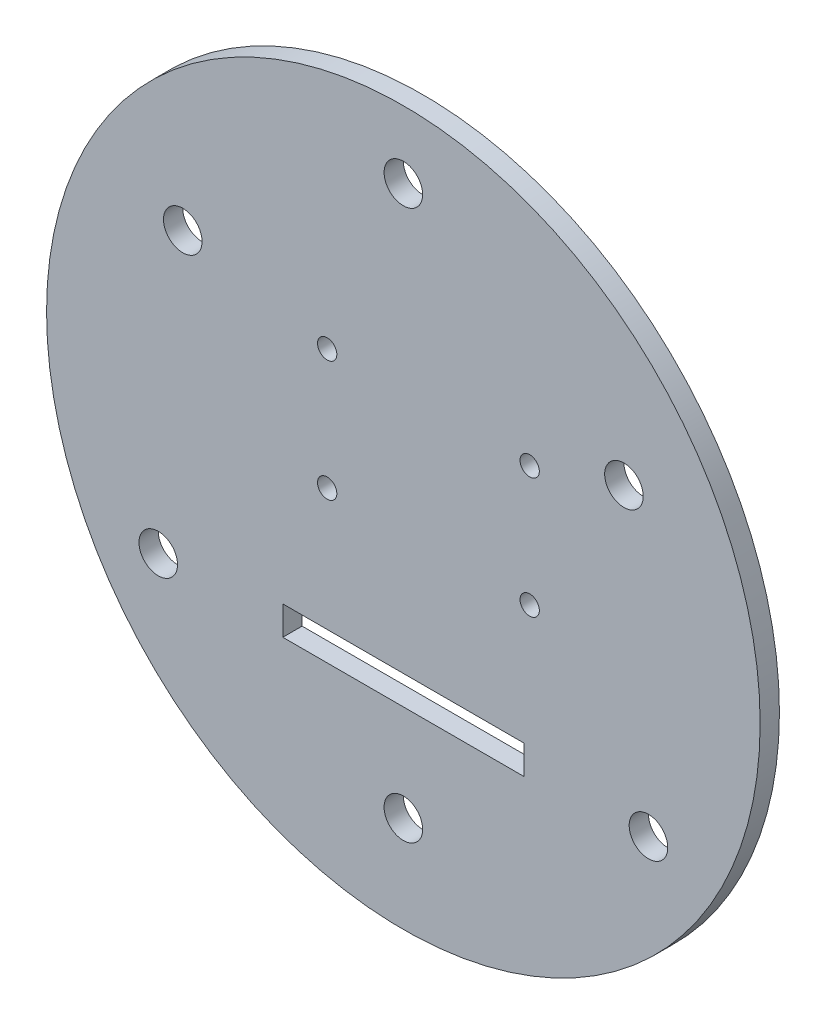
SolidWorks part; units mm, degrees
ref_plane "Plan de face" through (0, 0, 0) normal (0, 0, 1) x (1, 0, 0)
ref_plane "Plan de dessus" through (0, 0, 0) normal (0, 1, 0) x (1, 0, 0)
ref_plane "Plan de droite" through (0, 0, 0) normal (1, 0, 0) x (0, 0, -1)
sketch "Esquisse1" plane through (0, 0, 0) normal (0, 0, 1) x (1, 0, 0)
  line L0 (0, 0) -> (0, -27) construction
  line L1 (0, -27) -> (0, 30) construction
  line L2 (0, 0) -> (25.4165, -15.9375) construction
  line L3 (25.4165, -15.9375) -> (-22.8748, 14.3437) construction
  line L4 (-25.4165, -15.9375) -> (0, 0) construction
  line L5 (0, 0) -> (22.8748, 14.3437) construction
  line L6 (0, 30) -> (25.4165, -15.9375) construction
  line L8 (12.5, -14) -> (-12.5, -14)
  line L9 (12.5, -14) -> (12.5, -17)
  line L10 (12.5, -17) -> (-12.5, -17)
  line L11 (-12.5, -14) -> (-12.5, -17)
  circle A0 centre (0, 0) radius 37
  circle A1 centre (0, 30) radius 2
  circle A2 centre (-22.8748, 14.3437) radius 2
  circle A3 centre (-25.4165, -15.9375) radius 2
  circle A4 centre (0, -27) radius 2
  circle A5 centre (25.4165, -15.9375) radius 2
  circle A6 centre (22.8748, 14.3437) radius 2
  dimension "D1" = 74
  dimension "D11" = 4
  dimension "D12" = 4
  dimension "D13" = 4
  dimension "D14" = 4
  dimension "D15" = 4
  dimension "D16" = 4
  dimension "D2" = 27
  dimension "D3" = 57
  dimension "D4" = 57
  dimension "D5" = 30
  dimension "D6" = 30
  dimension "D7" = 27
  dimension "D8" = 52.5
  dimension "D9" = 52.5
  dimension "D10" = 47.25
  dimension "D17" = 25
  dimension "D18" = 3
  dimension "D19" = 10
  dimension "D20" = 12.5
extrude "Boss.-Extru.1" add sketch "Esquisse1" along normal blind 2
sketch "Esquisse2" plane through (0, 0, 0) normal (0, 0, -1) x (-1, 0, 0)
  line L0 (-16.55, 14.9) -> (-16.55, -13.5)
  line L1 (-12.55, 14.9) -> (12.55, 14.9)
  line L2 (-12.55, 14.9) -> (-12.55, -9.5)
  line L3 (-12.55, -9.5) -> (12.55, -9.5)
  line L4 (12.55, 14.9) -> (12.55, -9.5)
  line L5 (-16.55, -13.5) -> (16.55, -13.5)
  line L6 (16.55, -13.5) -> (16.55, 14.9)
  line L7 (16.55, 14.9) -> (12.55, 14.9)
  line L8 (-16.55, 14.9) -> (-12.55, 14.9)
  point P0 (0, 0)
  dimension "D1" = 25.1
  dimension "D2" = 9.5
  dimension "D3" = 24.4
  dimension "D4" = 4
  dimension "D5" = 4
  dimension "D6" = 4
  dimension "D7" = 12.55
extrude "Boss.-Extru.2" add sketch "Esquisse2" along normal blind 15 contours L8 L0 L5 L6 L7 L4 L3 L2 region at (14.55, 14.4639, 0)
sketch "Esquisse3" plane through (-12.55, 0, 0) normal (1, 0, 0) x (0, 0, -1)
  line L0 (15, 14.9) -> (0, 14.9) construction
  line L1 (10.625, 14.9) -> (8.625, 14.9)
  line L2 (10.625, 14.9) -> (10.625, -13.5)
  line L3 (10.625, -13.5) -> (8.625, -13.5)
  line L4 (8.625, 14.9) -> (8.625, -13.5)
  line L5 (15, -13.5) -> (0, -13.5) construction
  line L6 (0, 14.9) -> (7.5, 14.9) construction
  line L8 (5.625, 14.9) -> (7.625, 14.9)
  line L9 (5.625, 14.9) -> (5.625, -13.5)
  line L10 (5.625, -13.5) -> (7.625, -13.5)
  line L11 (7.625, 14.9) -> (7.625, -13.5)
  line L12 (8, 14.9) -> (8, -13.5) construction
  dimension "D1" = 2
  dimension "D2" = 0.625
  dimension "D3" = 2
  dimension "D4" = 1
  dimension "D5" = 0.375
  dimension "D6" = 0.5
extrude "Boss.-Extru.3" add sketch "Esquisse3" along normal blind 2.25 contours L11 L10 L9 L8 | L2 L3 L4 L1
sketch "Esquisse5" plane through (12.55, 0, 0) normal (-1, 0, 0) x (0, 0, 1)
  line L1 (-10.625, 14.9) -> (-8.625, 14.9)
  line L2 (-10.625, 14.9) -> (-10.625, -9.5)
  line L3 (-10.625, -9.5) -> (-8.625, -9.5)
  line L4 (-8.625, 14.9) -> (-8.625, -9.5)
  line L5 (-7.625, 14.9) -> (-5.625, 14.9)
  line L6 (-7.625, 14.9) -> (-7.625, -9.5)
  line L7 (-7.625, -9.5) -> (-5.625, -9.5)
  line L8 (-5.625, 14.9) -> (-5.625, -9.5)
extrude "Boss.-Extru.4" add sketch "Esquisse5" along normal blind 2.25
sketch "Esquisse7" plane through (0, 0, -15) normal (0, 0, -1) x (-1, 0, 0)
  line L1 (-16.55, 14.9) -> (16.55, 14.9)
  line L2 (-16.55, 14.9) -> (-16.55, -13.5)
  line L3 (-16.55, -13.5) -> (16.55, -13.5)
  line L4 (16.55, 14.9) -> (16.55, -13.5)
extrude "Boss.-Extru.5" add sketch "Esquisse7" against normal blind 1
sketch "Esquisse8" plane through (0, 0, -15) normal (0, 0, -1) x (-1, 0, 0)
  line L1 (-7.5, 7.5) -> (7.5, 7.5)
  line L2 (-7.5, 7.5) -> (-7.5, -7.5)
  line L3 (-7.5, -7.5) -> (7.5, -7.5)
  line L4 (7.5, 7.5) -> (7.5, -7.5)
  line L5 (-7.5, 7.5) -> (7.5, -7.5) construction
  line L6 (-7.5, -7.5) -> (7.5, 7.5) construction
  point P0 (0, 0)
  dimension "D1" = 15
  dimension "D2" = 15
extrude "Enlèv. mat.-Extru.1" cut sketch "Esquisse8" against normal blind 3 contours L3 L4 L1 L2
sketch "Esquisse9" plane through (0, -13.5, 0) normal (0, -1, 0) x (1, 0, 0)
  line L0 (16.55, 0) -> (-16.55, 0) construction
  line L1 (-10.5, -4.4) -> (10.5, -4.4)
  line L2 (-10.5, -4.4) -> (-10.5, -6.9)
  line L3 (-10.5, -6.9) -> (10.5, -6.9)
  line L4 (10.5, -4.4) -> (10.5, -6.9)
  line L6 (10.5, -4.4) -> (10.5, 0) construction
  line L7 (10.5, 0) -> (-10.5, 0) construction
  line L8 (-10.5, 0) -> (-10.5, -4.4) construction
  point P6 (0, -4.4)
  dimension "D1" = 21
  dimension "D2" = 2.5
  dimension "D3" = 4.4
  dimension "D4" = 0
extrude "Enlèv. mat.-Extru.2" cut sketch "Esquisse9" against normal blind 3 contours L1 L4 L3 L2
sketch "Esquisse10" plane through (0, 0, 2) normal (0, 0, 1) x (1, 0, 0)
  line L0 (16.55, -13.5) -> (-16.55, -13.5) construction
  line L1 (-16.55, -13.5) -> (-16.55, 14.9) construction
  line L2 (16.55, 14.9) -> (16.55, -13.5) construction
  line L3 (16.55, 14.9) -> (12.55, 14.9) construction
  line L4 (-16.55, 14.9) -> (-12.55, 14.9) construction
  circle A0 centre (-14.55, 8.9) radius 1
  circle A1 centre (-14.55, -11.5) radius 1
  circle A2 centre (14.55, -11.5) radius 1
  circle A3 centre (14.55, 8.9) radius 1
  dimension "D1" = 2
  dimension "D2" = 2
  dimension "D3" = 2
  dimension "D4" = 2
  dimension "D5" = 2
  dimension "D6" = 2
  dimension "D7" = 2
  dimension "D8" = 2
  dimension "D9" = 2
  dimension "D10" = 6
  dimension "D11" = 6
  dimension "D12" = 2
sketch "Esquisse11" plane through (0, 0, -15) normal (0, 0, -1) x (-1, 0, 0)
  line L1 (16.55, 14.9) -> (-16.55, 14.9)
  line L2 (16.55, 14.9) -> (16.55, -13.5)
  line L3 (16.55, -13.5) -> (-16.55, -13.5)
  line L4 (-16.55, 14.9) -> (-16.55, -13.5)
extrude "Enlèv. mat.-Extru.4" cut sketch "Esquisse11" against normal blind 15
sketch "Sketch1" plane through (0, 0, 0) normal (0, 0, -1) x (-1, 0, 0)
  line L1 (-6.6, -5.3) -> (1.4, -5.3) construction
  line L2 (-6.6, -5.3) -> (-6.6, 2.7) construction
  line L3 (-6.6, 2.7) -> (1.4, 2.7) construction
  line L4 (1.4, -5.3) -> (1.4, 2.7) construction
  line L5 (-6.6, -5.3) -> (1.4, 2.7) construction
  line L6 (-6.6, 2.7) -> (1.4, -5.3) construction
  line L7 (-13.1, -1.3) -> (7.9, -1.3) construction
  line L8 (-13.1, -1.3) -> (-13.1, 11.2) construction
  line L9 (-13.1, 11.2) -> (7.9, 11.2) construction
  line L10 (7.9, -1.3) -> (7.9, 11.2) construction
  line L11 (-13.1, -1.3) -> (7.9, 11.2) construction
  line L12 (-13.1, 11.2) -> (7.9, -1.3) construction
  circle A0 centre (0, 0) radius 37
  circle A1 centre (0, 0) radius 39.3 construction
  circle A2 centre (0, 0) radius 37 construction
  circle A3 centre (7.9, -1.3) radius 1
  circle A4 centre (-13.1, -1.3) radius 1
  circle A5 centre (-13.1, 11.2) radius 1.75
  circle A6 centre (7.9, 11.2) radius 1
  circle A7 centre (-13.1, -1.3) radius 1.75
  circle A8 centre (-13.1, 11.2) radius 1
  circle A9 centre (7.9, 11.2) radius 1.75
  circle A10 centre (7.9, -1.3) radius 1.75
  point P11 (0, 0)
  point P22 (-2.6, 4.95)
  point P24 (0, 0)
  point P25 (8, -0.9249)
  point P26 (0, 0)
  point P27 (0, 0)
  point P28 (0, 0)
  point P29 (0, 0)
  point P30 (0, 0)
  point P31 (0, 0)
  point P33 (-2.6, -1.3)
  dimension "D3" = 2
  dimension "D6" = 2
  dimension "D7" = 2
  dimension "D8" = 3.5
  dimension "D9" = 3.5
  dimension "D10" = 2
  dimension "D11" = 3.5
  dimension "D12" = 3.5
  dimension "D1" = 8
  dimension "D2" = 8
  dimension "D4" = 21
  dimension "D5" = 12.5
  dimension "D13" = 2.6
  dimension "D14" = 1.3
extrude "Boss-Extrude1" add sketch "Sketch1" along normal blind 10 contours A10 A3 | A9 A6 | A5 A8 | A7 A4 region at (14.8005, 11.2, 0) region at (14.8005, -1.3, 0) region at (-6.1995, 11.2, 0) region at (-6.1995, -1.3, 0)
extrude "Cut-Extrude1" cut sketch "Sketch1<3>" against normal blind 10 contours A8 | A4 | A3 | A6 region at (-7.9, -1.3, 0) region at (13.1, -1.3, 0) region at (-7.9, 11.2, 0) region at (13.1, 11.2, 0)
sketch "Sketch1<3>" plane through (0, 0, 0) normal (0, 0, -1) x (-1, 0, 0) same geometry as "Sketch1"
